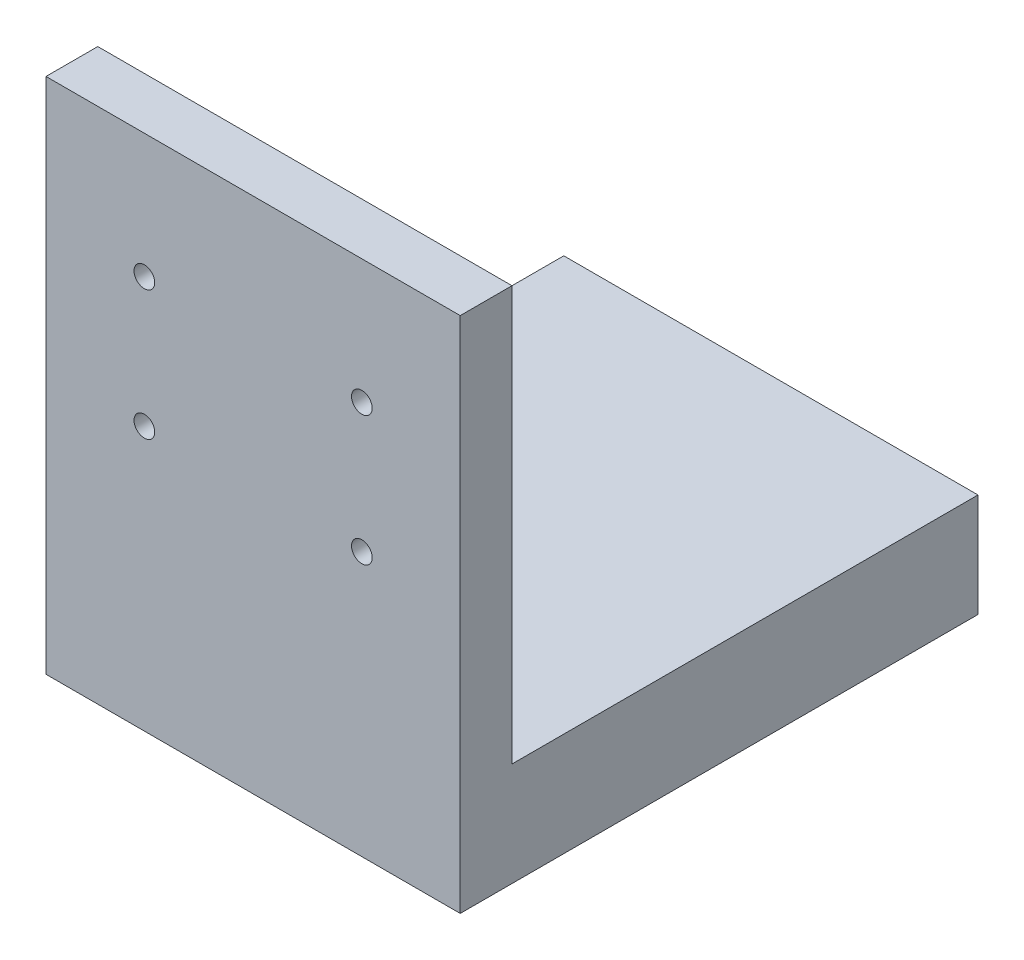
SolidWorks part; units mm, degrees
ref_plane "Front Plane" through (0, 0, 0) normal (0, 0, 1) x (1, 0, 0)
ref_plane "Top Plane" through (0, 0, 0) normal (0, 1, 0) x (1, 0, 0)
ref_plane "Right Plane" through (0, 0, 0) normal (1, 0, 0) x (0, 0, -1)
sketch "Sketch1" plane through (0, 0, 0) normal (0, 1, 0) x (1, 0, 0)
  line L1 (-20, -25) -> (20, -25)
  line L2 (-20, -25) -> (-20, 25)
  line L3 (-20, 25) -> (20, 25)
  line L4 (20, -25) -> (20, 25)
  line L5 (-20, -25) -> (20, 25) construction
  line L6 (-20, 25) -> (20, -25) construction
  point P0 (0, 0)
  dimension "D1" = 50
  dimension "D2" = 40
extrude "Boss-Extrude1" add sketch "Sketch1" along normal blind 10
sketch "Sketch2" plane through (0, 10, 0) normal (0, 1, 0) x (1, 0, 0)
  line L0 (20, -25) -> (20, 25) construction
  line L1 (-20, -25) -> (20, -25)
  line L2 (-20, -25) -> (-20, -20)
  line L3 (-20, -20) -> (20, -20)
  line L4 (20, -25) -> (20, -20)
  dimension "D1" = 5
extrude "Boss-Extrude2" add sketch "Sketch2" along normal blind 40
sketch "Sketch3" plane through (0, 0, 25) normal (0, 0, 1) x (1, 0, 0)
  circle A0 centre (10.5, 25.5) radius 1 construction
  circle A1 centre (-10.5, 25.5) radius 1 construction
  circle A2 centre (10.5, 38) radius 1 construction
  circle A3 centre (-10.5, 38) radius 1 construction
  circle A4 centre (10.5, 25.5) radius 1
  circle A5 centre (-10.5, 25.5) radius 1
  circle A6 centre (10.5, 38) radius 1
  circle A7 centre (-10.5, 38) radius 1
hole_wizard "Ø2.0mm Dowel Hole1" positions "Sketch4" profile "Sketch5" hole size "Ø2.0" standard "ANSI Metric" end condition through all
sketch "Sketch4" plane through (0, 0, 25) normal (0, 0, 1) x (1, 0, 0)
  point P0 (-10.5, 38)
  point P3 (10.5, 38)
  point P6 (-10.5, 25.5)
  point P9 (10.5, 25.5)
sketch "Sketch5" plane through (-10.5, 38, 25) normal (1, 0, 0) x (0, -1, 0)
  line L0 (0, 0) -> (0, 50)
  line L1 (0, 50) -> (1, 50)
  line L2 (1, 50) -> (1, 0)
  line L5 (1, 0) -> (0, 0)
  line L11 (0, -6.35) -> (0, 107.95) construction
  dimension "Thru Hole Dia." = 2
  dimension "Thru Hole Depth" = 50
